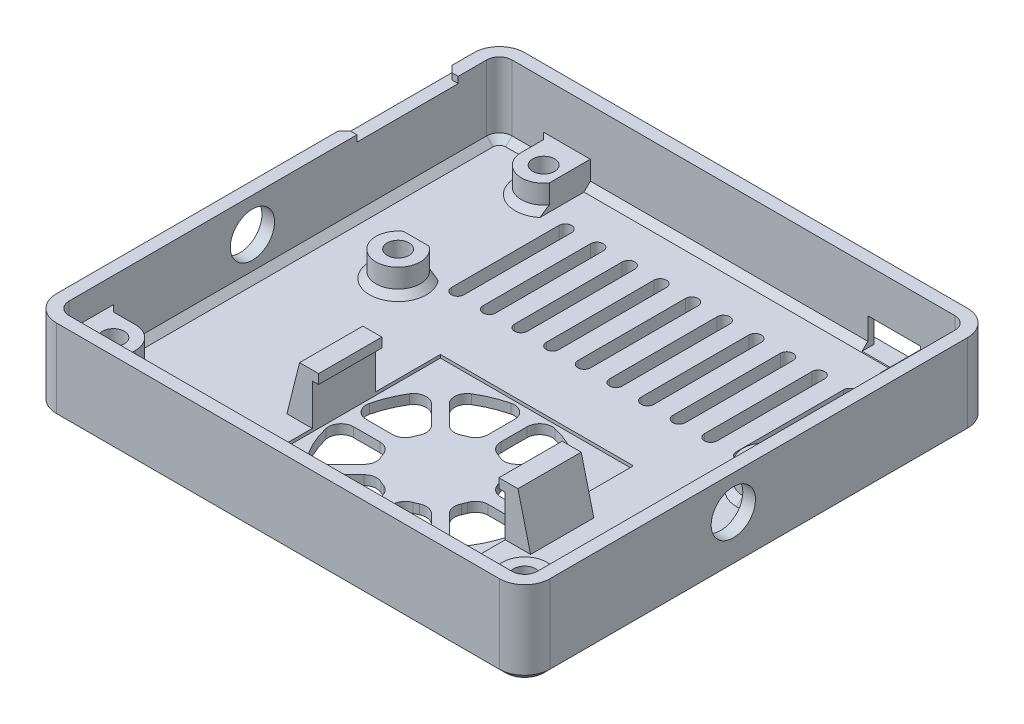
SolidWorks part; units mm, degrees
ref_plane "Front Plane" through (0, 0, 0) normal (0, 0, 1) x (1, 0, 0)
ref_plane "Top Plane" through (0, 0, 0) normal (0, 1, 0) x (1, 0, 0)
ref_plane "Right Plane" through (0, 0, 0) normal (1, 0, 0) x (0, 0, -1)
sketch "Sketch1" plane through (0, 0, 0) normal (0, 1, 0) x (1, 0, 0)
  line L0 (-65.617, -16.3721) -> (-0.617, -16.3721)
  line L1 (-62.117, 10.1279) -> (-4.117, 10.1279)
  line L2 (-62.117, 10.1279) -> (-62.117, -12.8721)
  line L3 (-65.617, 13.6279) -> (-0.617, 13.6279)
  line L4 (-65.617, 13.6279) -> (-65.617, -16.3721)
  line L5 (-62.117, -12.8721) -> (-4.117, -12.8721)
  line L6 (-0.617, 13.6279) -> (-0.617, -16.3721)
  line L7 (-4.117, 10.1279) -> (-4.117, -12.8721)
  line L8 (-24.217, 16.7282) -> (-24.217, 15.4455)
  line L9 (-11.617, 16.7282) -> (-11.617, 15.4455)
  dimension "D1" = 65
  dimension "D2" = 30
  dimension "D3" = 58
  dimension "D4" = 23
  dimension "D5" = 3.5
  dimension "D6" = 3.5
sketch "Sketch2" plane through (0, 0, 0) normal (0, 1, 0) x (1, 0, 0)
  line L6 (-73.617, 13.6279) -> (-73.617, -16.3721)
  line L7 (-73.617, 12.6279) -> (-73.617, -53.3721)
  line L10 (-71.617, -55.3721) -> (-1.617, -55.3721)
  line L11 (-75.617, 12.6279) -> (-75.617, -53.3721)
  line L12 (0.383, 14.6279) -> (0.383, -16.3721)
  line L13 (-65.617, 14.6279) -> (0.383, 14.6279)
  line L14 (0.383, 12.6279) -> (0.383, -53.3721)
  line L15 (-71.617, 14.6279) -> (-1.617, 14.6279)
  line L16 (-71.617, -57.3721) -> (-1.617, -57.3721)
  line L17 (2.383, 12.6279) -> (2.383, -53.3721)
  line L18 (-71.617, 16.6279) -> (-1.617, 16.6279)
  arc A0 (-71.617, -55.3721) -> (-73.617, -53.3721) centre (-71.617, -53.3721) cw
  arc A1 (-1.617, -55.3721) -> (0.383, -53.3721) centre (-1.617, -53.3721) ccw
  arc A2 (0.383, 12.6279) -> (-1.617, 14.6279) centre (-1.617, 12.6279) ccw
  arc A3 (-71.617, 14.6279) -> (-73.617, 12.6279) centre (-71.617, 12.6279) ccw
  arc A4 (-71.617, -57.3721) -> (-75.617, -53.3721) centre (-71.617, -53.3721) cw
  arc A5 (-1.617, -57.3721) -> (2.383, -53.3721) centre (-1.617, -53.3721) ccw
  arc A6 (2.383, 12.6279) -> (-1.617, 16.6279) centre (-1.617, 12.6279) ccw
  arc A7 (-71.617, 16.6279) -> (-75.617, 12.6279) centre (-71.617, 12.6279) ccw
  dimension "D4" = 2
  dimension "D3" = 70
  dimension "D1" = 8
  dimension "D2" = 1
  dimension "D5" = 2
extrude "Boss-Extrude1" add sketch "Sketch2" along normal blind 13.4
extrude "Boss-Extrude2" add sketch "Sketch2<3>" along normal blind 2 contours L15 A3 L7 A0 L10 A1 L14 A2 region at (-36.617, 0, 20.3721)
sketch "Sketch2<3>" plane through (0, 0, 0) normal (0, 1, 0) x (1, 0, 0) same geometry as "Sketch2"
sketch "Sketch4" plane through (0, 2, 0) normal (0, 1, 0) x (1, 0, 0)
  line L0 (-59.2343, 14.6279) -> (-59.2343, 8.1428)
  line L1 (-1.617, 14.6279) -> (-71.617, 14.6279) construction
  line L2 (-4.117, 6.6279) -> (0.383, 6.6279)
  line L3 (0.383, -53.3721) -> (0.383, 12.6279) construction
  line L4 (0.383, 6.6279) -> (0.383, 12.6279)
  line L5 (-7.0825, 14.6279) -> (-1.617, 14.6279)
  line L6 (-4.117, -9.3721) -> (0.383, -9.3721)
  line L7 (0.383, -9.3721) -> (0.383, -16.3721)
  line L8 (0.383, -16.3721) -> (-4.117, -16.3721)
  line L9 (-64.1397, -10.0158) -> (-60.0943, -10.0158)
  line L10 (-59.2343, 14.6279) -> (-65.617, 14.6279)
  line L11 (-65.617, 14.6279) -> (-65.617, 10.1279)
  line L12 (-7.0825, 14.6279) -> (-7.0825, 8.269)
  arc A0 (-7.0825, 8.269) -> (-4.117, 6.6279) centre (-4.117, 10.1279) ccw
  arc A1 (-4.117, -9.3721) -> (-4.117, -16.3721) centre (-4.117, -12.8721) ccw
  arc A2 (-64.1397, -10.0158) -> (-60.0943, -10.0158) centre (-62.117, -12.8721) ccw
  arc A3 (-65.617, 10.1279) -> (-59.2343, 8.1428) centre (-62.117, 10.1279) ccw
  arc A4 (0.383, 12.6279) -> (-1.617, 14.6279) centre (-1.617, 12.6279) ccw
  dimension "D1" = 2
extrude "Boss-Extrude3" add sketch "Sketch4" along normal offset from surface (4 mm away) 7.4 up to face at (-36.617, 13.4, 20.3721)
hole_wizard "CSK for #4 Flat Head Socket Cap Screw1" positions "Sketch6" profile "Sketch5" countersink size "#4" standard "ANSI Inch" end condition through all
sketch "Sketch6" plane through (0, 0, 0) normal (0, -1, 0) x (-1, 0, 0)
  point P0 (4.117, 10.1279)
  point P4 (62.117, 10.1279)
  point P8 (4.117, -12.8721)
  point P12 (62.117, -12.8721)
sketch "Sketch5" plane through (-4.117, 0, -10.1279) normal (1, 0, 0) x (0, 0, -1)
  line L0 (0, 0) -> (0, 13.4)
  line L1 (0, 13.4) -> (1.7272, 13.4)
  line L2 (1.7272, 13.4) -> (1.7272, 1.8805)
  line L3 (1.7272, 1.8805) -> (3.3619, 0)
  line L5 (3.3619, 0) -> (0, 0)
  line L6 (-1.7272, 1.8805) -> (-3.3619, 0) construction
  line L11 (0, -6.35) -> (0, 107.95) construction
  dimension "Thru Hole Dia." = 3.4544
  dimension "Thru Hole Depth" = 13.4
  dimension "Near C'Sink Dia." = 6.7237
  dimension "Near C'Sink Angle" = 82
sketch "Sketch7" plane through (0, 0, -16.6279) normal (0, 0, -1) x (-1, 0, 0)
  line L0 (11.2325, 6.5) -> (11.2325, 2.1) construction
  line L1 (7.0825, 6.5) -> (15.3825, 6.5)
  line L2 (7.0825, 6.5) -> (7.0825, 2.1)
  line L3 (7.0825, 2.1) -> (15.3825, 2.1)
  line L4 (15.3825, 6.5) -> (15.3825, 2.1)
  line L5 (1.617, 6) -> (7.0825, 6) construction
  line L7 (7.0825, 6) -> (7.0825, 2) construction
  dimension "D1" = 8.3
  dimension "D2" = 0.5
  dimension "D3" = 0
  dimension "D4" = 4.4
extrude "Cut-Extrude1" cut sketch "Sketch7" against normal up to next
sketch "Sketch9" plane through (0, 2, 0) normal (0, 1, 0) x (1, 0, 0)
  line L0 (0.383, -16.3721) -> (0.383, -53.3721) construction
  line L1 (-71.617, -55.3721) -> (-1.617, -55.3721) construction
  line L2 (-73.617, 12.6279) -> (-73.617, -53.3721) construction
  line L3 (-69.117, -47.3721) -> (-73.617, -47.3721)
  line L4 (-65.617, -50.8721) -> (-65.617, -55.3721)
  line L5 (-71.617, -55.3721) -> (-1.617, -55.3721) construction
  line L6 (-73.617, -47.3721) -> (-73.617, -53.3721)
  line L7 (-65.617, -55.3721) -> (-71.617, -55.3721)
  line L8 (-4.117, -47.3721) -> (0.383, -47.3721)
  line L9 (0.383, -47.3721) -> (0.383, -53.3721)
  line L10 (-7.617, -50.8721) -> (-7.617, -55.3721)
  line L11 (-7.617, -55.3721) -> (-1.617, -55.3721)
  arc A0 (-4.117, -47.3721) -> (-7.617, -50.8721) centre (-4.117, -50.8721) ccw
  arc A1 (-65.617, -50.8721) -> (-69.117, -47.3721) centre (-69.117, -50.8721) ccw
  arc A2 (-73.617, -53.3721) -> (-71.617, -55.3721) centre (-71.617, -53.3721) ccw
  arc A3 (-1.617, -55.3721) -> (0.383, -53.3721) centre (-1.617, -53.3721) ccw
  dimension "D1" = 4.5
  dimension "D2" = 4.5
  dimension "D3" = 4.5
  dimension "D4" = 4.5
  dimension "D5" = 2
  dimension "D6" = 2
extrude "Boss-Extrude4" add sketch "Sketch9" along normal offset from surface (7.4 mm away) 4 up to face at (-36.617, 13.4, 20.3721)
hole_wizard "CSK for #4 Flat Head Socket Cap Screw2" positions "Sketch11" profile "Sketch10" countersink size "#4" standard "ANSI Inch" end condition through all
sketch "Sketch11" plane through (0, 0, 0) normal (0, -1, 0) x (-1, 0, 0)
  point P0 (4.117, -50.8721)
  point P4 (69.117, -50.8721)
sketch "Sketch10" plane through (-4.117, 0, 50.8721) normal (1, 0, 0) x (0, 0, -1)
  line L0 (0, 0) -> (0, 13.4)
  line L1 (0, 13.4) -> (1.7272, 13.4)
  line L2 (1.7272, 13.4) -> (1.7272, 1.8805)
  line L3 (1.7272, 1.8805) -> (3.3619, 0)
  line L5 (3.3619, 0) -> (0, 0)
  line L6 (-1.7272, 1.8805) -> (-3.3619, 0) construction
  line L11 (0, -6.35) -> (0, 107.95) construction
  dimension "Thru Hole Dia." = 3.4544
  dimension "Thru Hole Depth" = 13.4
  dimension "Near C'Sink Dia." = 6.7237
  dimension "Near C'Sink Angle" = 82
chamfer "Chamfer1" distance 1 angle 45 8 edges at (-65.617, 4, -14.6279) (-65.617, 5.7, 55.3721) (-73.617, 5.7, 47.3721) (0.383, 4, 9.3721) (0.383, 4, -6.6279) (0.383, 4, 16.3721) (0.383, 5.7, 47.3721) (-7.617, 5.7, 55.3721)
chamfer "Chamfer2" distance 1 angle 45 21 edges at (-62.117, 2, 16.3721) (-65.617, 2, -11.8779) (-63.1564, 2, -6.7858) (-2.367, 2, -6.6279) (-5.8117, 2, -7.0655) (0.383, 2, 1.3721) (-2.367, 2, 9.3721) (-2.367, 2, 16.3721) (0.383, 2, 31.8721) (-2.367, 2, 47.3721) (-7.617, 2, 52.6221) (-6.5919, 2, 48.3973) (-36.617, 2, 55.3721) (-65.617, 2, 52.6221) (-70.867, 2, 47.3721) (-66.6421, 2, 48.3973) (-69.117, 2, -14.6279) (-73.0312, 2, -14.0421) (-73.617, 2, 16.8721) (-7.617, 2, 12.8721) (-33.1584, 2, -14.6279)
chamfer "Chamfer3" distance 1 angle 45 8 edges at (2.383, 0, 20.3721) (1.2114, 0, -15.4563) (1.2114, 0, 56.2006) (-36.617, 0, -16.6279) (-36.617, 0, 57.3721) (-74.4454, 0, -15.4563) (-74.4454, 0, 56.2006) (-75.617, 0, 20.3721)
chamfer "Chamfer4" distance 1 angle 45 2 edges at (-15.3825, 4.3, -16.6279) (-7.0825, 4.3, -16.6279)
sketch "Sketch12" plane through (0, 0, 0) normal (0, -1, 0) x (1, 0, 0)
  line L0 (-55.6605, 9.9113) -> (-55.6605, -7.0887) construction
  line L1 (-54.6605, 9.9113) -> (-54.6605, -7.0887)
  line L2 (-56.6605, 9.9113) -> (-56.6605, -7.0887)
  line L3 (-50.6605, 9.9113) -> (-50.6605, -7.0887) construction
  line L4 (-49.6605, 9.9113) -> (-49.6605, -7.0887)
  line L5 (-51.6605, 9.9113) -> (-51.6605, -7.0887)
  line L6 (-45.6605, 9.9113) -> (-45.6605, -7.0887) construction
  line L7 (-44.6605, 9.9113) -> (-44.6605, -7.0887)
  line L8 (-46.6605, 9.9113) -> (-46.6605, -7.0887)
  line L9 (-40.6605, 9.9113) -> (-40.6605, -7.0887) construction
  line L10 (-39.6605, 9.9113) -> (-39.6605, -7.0887)
  line L11 (-41.6605, 9.9113) -> (-41.6605, -7.0887)
  line L12 (-35.6605, 9.9113) -> (-35.6605, -7.0887) construction
  line L13 (-34.6605, 9.9113) -> (-34.6605, -7.0887)
  line L14 (-36.6605, 9.9113) -> (-36.6605, -7.0887)
  line L15 (-30.6605, 9.9113) -> (-30.6605, -7.0887) construction
  line L16 (-29.6605, 9.9113) -> (-29.6605, -7.0887)
  line L17 (-31.6605, 9.9113) -> (-31.6605, -7.0887)
  line L18 (-25.6605, 9.9113) -> (-25.6605, -7.0887) construction
  line L19 (-24.6605, 9.9113) -> (-24.6605, -7.0887)
  line L20 (-26.6605, 9.9113) -> (-26.6605, -7.0887)
  line L21 (-20.6605, 9.9113) -> (-20.6605, -7.0887) construction
  line L22 (-19.6605, 9.9113) -> (-19.6605, -7.0887)
  line L23 (-21.6605, 9.9113) -> (-21.6605, -7.0887)
  line L24 (-15.6605, 9.9113) -> (-15.6605, -7.0887) construction
  line L25 (-14.6605, 9.9113) -> (-14.6605, -7.0887)
  line L26 (-16.6605, 9.9113) -> (-16.6605, -7.0887)
  line L27 (-10.6605, 9.9113) -> (-10.6605, -7.0887) construction
  line L28 (-9.6605, 9.9113) -> (-9.6605, -7.0887)
  line L29 (-11.6605, 9.9113) -> (-11.6605, -7.0887)
  arc A0 (-54.6605, 9.9113) -> (-56.6605, 9.9113) centre (-55.6605, 9.9113) ccw
  arc A1 (-56.6605, -7.0887) -> (-54.6605, -7.0887) centre (-55.6605, -7.0887) ccw
  arc A2 (-49.6605, 9.9113) -> (-51.6605, 9.9113) centre (-50.6605, 9.9113) ccw
  arc A3 (-51.6605, -7.0887) -> (-49.6605, -7.0887) centre (-50.6605, -7.0887) ccw
  arc A4 (-44.6605, 9.9113) -> (-46.6605, 9.9113) centre (-45.6605, 9.9113) ccw
  arc A5 (-46.6605, -7.0887) -> (-44.6605, -7.0887) centre (-45.6605, -7.0887) ccw
  arc A6 (-39.6605, 9.9113) -> (-41.6605, 9.9113) centre (-40.6605, 9.9113) ccw
  arc A7 (-41.6605, -7.0887) -> (-39.6605, -7.0887) centre (-40.6605, -7.0887) ccw
  arc A8 (-34.6605, 9.9113) -> (-36.6605, 9.9113) centre (-35.6605, 9.9113) ccw
  arc A9 (-36.6605, -7.0887) -> (-34.6605, -7.0887) centre (-35.6605, -7.0887) ccw
  arc A10 (-29.6605, 9.9113) -> (-31.6605, 9.9113) centre (-30.6605, 9.9113) ccw
  arc A11 (-31.6605, -7.0887) -> (-29.6605, -7.0887) centre (-30.6605, -7.0887) ccw
  arc A12 (-24.6605, 9.9113) -> (-26.6605, 9.9113) centre (-25.6605, 9.9113) ccw
  arc A13 (-26.6605, -7.0887) -> (-24.6605, -7.0887) centre (-25.6605, -7.0887) ccw
  arc A14 (-19.6605, 9.9113) -> (-21.6605, 9.9113) centre (-20.6605, 9.9113) ccw
  arc A15 (-21.6605, -7.0887) -> (-19.6605, -7.0887) centre (-20.6605, -7.0887) ccw
  arc A16 (-14.6605, 9.9113) -> (-16.6605, 9.9113) centre (-15.6605, 9.9113) ccw
  arc A17 (-16.6605, -7.0887) -> (-14.6605, -7.0887) centre (-15.6605, -7.0887) ccw
  arc A18 (-9.6605, 9.9113) -> (-11.6605, 9.9113) centre (-10.6605, 9.9113) ccw
  arc A19 (-11.6605, -7.0887) -> (-9.6605, -7.0887) centre (-10.6605, -7.0887) ccw
  point P2 (-55.6605, 1.4113)
  point P10 (-50.6605, 1.4113)
  point P17 (-45.6605, 1.4113)
  point P24 (-40.6605, 1.4113)
  point P31 (-35.6605, 1.4113)
  point P38 (-30.6605, 1.4113)
  point P45 (-25.6605, 1.4113)
  point P52 (-20.6605, 1.4113)
  point P59 (-15.6605, 1.4113)
  point P66 (-10.6605, 1.4113)
  dimension "D1" = 2
  dimension "D2" = 17
  dimension "D3" = 10
extrude "Cut-Extrude2" cut sketch "Sketch12" against normal up to next
sketch "Sketch13" plane through (0, 2, 0) normal (0, 1, 0) x (1, 0, 0)
  line L1 (-17.867, -50.4402) -> (-48.367, -50.4402)
  line L2 (-17.867, -50.4402) -> (-17.867, -19.9402)
  line L3 (-17.867, -19.9402) -> (-48.367, -19.9402)
  line L4 (-48.367, -50.4402) -> (-48.367, -19.9402)
  dimension "D1" = 30.5
  dimension "D2" = 30.5
extrude "Cut-Extrude3" cut sketch "Sketch13" against normal blind 0.5
sketch "Sketch14" plane through (0, 2, 0) normal (0, 1, 0) x (1, 0, 0)
  line L0 (-48.367, -40.1902) -> (-50.367, -40.1902)
  line L1 (-15.867, -40.1902) -> (-17.867, -40.1902)
  line L2 (-15.867, -40.1902) -> (-15.867, -30.1902)
  line L3 (-15.867, -30.1902) -> (-17.867, -30.1902)
  line L4 (-17.867, -40.1902) -> (-17.867, -30.1902)
  line L5 (-48.367, -30.1902) -> (-50.367, -30.1902)
  line L6 (-50.367, -40.1902) -> (-50.367, -30.1902)
  line L7 (-48.367, -40.1902) -> (-48.367, -30.1902)
  dimension "D1" = 10
  dimension "D2" = 2
  dimension "D3" = 10
extrude "Boss-Extrude5" add sketch "Sketch14" along normal blind 8
sketch "Sketch15" plane through (-17.867, 0, 0) normal (-1, 0, 0) x (0, 0, 1)
  line L0 (30.1902, 10) -> (30.1902, 2) construction
  line L1 (40.1902, 10) -> (30.1902, 10)
  line L2 (40.1902, 10) -> (40.1902, 8.5)
  line L3 (40.1902, 8.5) -> (30.1902, 8.5)
  line L4 (30.1902, 10) -> (30.1902, 8.5)
  line L5 (30.1902, 10) -> (40.1902, 10) construction
  dimension "D1" = 1.5
extrude "Boss-Extrude6" add sketch "Sketch15" along normal blind 1
sketch "Sketch16" plane through (-48.367, 0, 0) normal (1, 0, 0) x (0, 0, -1)
  line L0 (-30.1902, 10) -> (-30.1902, 2) construction
  line L1 (-40.1902, 10) -> (-30.1902, 10)
  line L2 (-40.1902, 10) -> (-40.1902, 8.5)
  line L3 (-40.1902, 8.5) -> (-30.1902, 8.5)
  line L4 (-30.1902, 10) -> (-30.1902, 8.5)
  dimension "D1" = 1.5
extrude "Boss-Extrude7" add sketch "Sketch16" along normal blind 1
chamfer "Chamfer5" distance 2 angle 76 2 edges at (-50.367, 2, 35.1902) (-15.867, 2, 35.1902) first distance on face at (-10.6605, 2, 1.4113)
sketch "Sketch17" plane through (0, 1.5, 0) normal (0, 1, 0) x (1, 0, 0)
  line L0 (-41.3961, -25.4969) -> (-38.4532, -28.4398)
  line L1 (-34.117, -22.4818) -> (-34.117, -26.6437)
  line L2 (-32.117, -22.4818) -> (-32.117, -26.6437)
  line L3 (-24.8379, -25.4969) -> (-27.7808, -28.4398)
  line L4 (-23.4236, -26.9111) -> (-26.3666, -29.854)
  line L5 (-20.4085, -34.1902) -> (-24.5705, -34.1902)
  line L6 (-20.4085, -36.1902) -> (-24.5705, -36.1902)
  line L7 (-23.4236, -43.4693) -> (-26.3666, -40.5264)
  line L8 (-24.8379, -44.8835) -> (-27.7808, -41.9406)
  line L9 (-32.117, -47.8987) -> (-32.117, -43.7367)
  line L10 (-34.117, -47.8987) -> (-34.117, -43.7367)
  line L11 (-41.3961, -44.8835) -> (-38.4532, -41.9406)
  line L12 (-42.8103, -43.4693) -> (-39.8674, -40.5264)
  line L13 (-45.8254, -36.1902) -> (-41.6635, -36.1902)
  line L14 (-45.8254, -34.1902) -> (-41.6635, -34.1902)
  line L15 (-42.8103, -26.9111) -> (-39.8674, -29.854)
  arc A0 (-45.9258, -27.2738) -> (-47.7719, -31.7307) centre (-33.117, -35.1902) ccw
  arc A1 (-39.4788, -32.1342) -> (-39.7764, -32.8526) centre (-33.117, -35.1902) ccw
  arc A2 (-39.4788, -32.1342) -> (-39.8674, -29.854) centre (-41.2816, -31.2682) ccw
  arc A3 (-41.6635, -34.1902) -> (-39.7764, -32.8526) centre (-41.6635, -32.1902) ccw
  arc A4 (-45.8254, -34.1902) -> (-47.7719, -31.7307) centre (-45.8254, -32.1902) cw
  arc A5 (-42.8103, -26.9111) -> (-45.9258, -27.2738) centre (-44.2245, -28.3253) ccw
  arc A6 (-36.5765, -20.5353) -> (-41.0334, -22.3814) centre (-33.117, -35.1902) ccw
  arc A7 (-35.4546, -28.5308) -> (-36.173, -28.8284) centre (-33.117, -35.1902) ccw
  arc A8 (-35.4546, -28.5308) -> (-34.117, -26.6437) centre (-36.117, -26.6437) ccw
  arc A9 (-38.4532, -28.4398) -> (-36.173, -28.8284) centre (-37.039, -27.0256) ccw
  arc A10 (-41.3961, -25.4969) -> (-41.0334, -22.3814) centre (-39.9819, -24.0827) cw
  arc A11 (-34.117, -22.4818) -> (-36.5765, -20.5353) centre (-36.117, -22.4818) ccw
  arc A12 (-25.2006, -22.3814) -> (-29.6575, -20.5353) centre (-33.117, -35.1902) ccw
  arc A13 (-30.061, -28.8284) -> (-30.7794, -28.5308) centre (-33.117, -35.1902) ccw
  arc A14 (-30.061, -28.8284) -> (-27.7808, -28.4398) centre (-29.195, -27.0256) ccw
  arc A15 (-32.117, -26.6437) -> (-30.7794, -28.5308) centre (-30.117, -26.6437) ccw
  arc A16 (-32.117, -22.4818) -> (-29.6575, -20.5353) centre (-30.117, -22.4818) cw
  arc A17 (-24.8379, -25.4969) -> (-25.2006, -22.3814) centre (-26.2521, -24.0827) ccw
  arc A18 (-18.462, -31.7307) -> (-20.3081, -27.2738) centre (-33.117, -35.1902) ccw
  arc A19 (-26.4576, -32.8526) -> (-26.7552, -32.1342) centre (-33.117, -35.1902) ccw
  arc A20 (-26.4576, -32.8526) -> (-24.5705, -34.1902) centre (-24.5705, -32.1902) ccw
  arc A21 (-26.3666, -29.854) -> (-26.7552, -32.1342) centre (-24.9524, -31.2682) ccw
  arc A22 (-23.4236, -26.9111) -> (-20.3081, -27.2738) centre (-22.0094, -28.3253) cw
  arc A23 (-20.4085, -34.1902) -> (-18.462, -31.7307) centre (-20.4085, -32.1902) ccw
  arc A24 (-20.3081, -43.1066) -> (-18.462, -38.6497) centre (-33.117, -35.1902) ccw
  arc A25 (-26.7552, -38.2462) -> (-26.4576, -37.5278) centre (-33.117, -35.1902) ccw
  arc A26 (-26.7552, -38.2462) -> (-26.3666, -40.5264) centre (-24.9524, -39.1122) ccw
  arc A27 (-24.5705, -36.1902) -> (-26.4576, -37.5278) centre (-24.5705, -38.1902) ccw
  arc A28 (-20.4085, -36.1902) -> (-18.462, -38.6497) centre (-20.4085, -38.1902) cw
  arc A29 (-23.4236, -43.4693) -> (-20.3081, -43.1066) centre (-22.0094, -42.0551) ccw
  arc A30 (-29.6575, -49.8452) -> (-25.2006, -47.9991) centre (-33.117, -35.1902) ccw
  arc A31 (-30.7794, -41.8496) -> (-30.061, -41.552) centre (-33.117, -35.1902) ccw
  arc A32 (-30.7794, -41.8496) -> (-32.117, -43.7367) centre (-30.117, -43.7367) ccw
  arc A33 (-27.7808, -41.9406) -> (-30.061, -41.552) centre (-29.195, -43.3548) ccw
  arc A34 (-24.8379, -44.8835) -> (-25.2006, -47.9991) centre (-26.2521, -46.2978) cw
  arc A35 (-32.117, -47.8987) -> (-29.6575, -49.8452) centre (-30.117, -47.8987) ccw
  arc A36 (-41.0334, -47.9991) -> (-36.5765, -49.8452) centre (-33.117, -35.1902) ccw
  arc A37 (-36.173, -41.552) -> (-35.4546, -41.8496) centre (-33.117, -35.1902) ccw
  arc A38 (-36.173, -41.552) -> (-38.4532, -41.9406) centre (-37.039, -43.3548) ccw
  arc A39 (-34.117, -43.7367) -> (-35.4546, -41.8496) centre (-36.117, -43.7367) ccw
  arc A40 (-34.117, -47.8987) -> (-36.5765, -49.8452) centre (-36.117, -47.8987) cw
  arc A41 (-41.3961, -44.8835) -> (-41.0334, -47.9991) centre (-39.9819, -46.2978) ccw
  arc A42 (-47.7719, -38.6497) -> (-45.9258, -43.1066) centre (-33.117, -35.1902) ccw
  arc A43 (-39.7764, -37.5278) -> (-39.4788, -38.2462) centre (-33.117, -35.1902) ccw
  arc A44 (-39.7764, -37.5278) -> (-41.6635, -36.1902) centre (-41.6635, -38.1902) ccw
  arc A45 (-39.8674, -40.5264) -> (-39.4788, -38.2462) centre (-41.2816, -39.1122) ccw
  arc A46 (-42.8103, -43.4693) -> (-45.9258, -43.1066) centre (-44.2245, -42.0551) cw
  arc A47 (-45.8254, -36.1902) -> (-47.7719, -38.6497) centre (-45.8254, -38.1902) ccw
  point P41 (-33.117, -35.1902)
  point P98 (-33.117, -35.1902)
  dimension "D1" = 2
extrude "Cut-Extrude4" cut sketch "Sketch17" against normal through all
sketch "Sketch18" plane through (-73.617, 0, 0) normal (1, 0, 0) x (0, 0, -1)
  circle A0 centre (-24.3941, 7.9996) radius 3.5
  dimension "D1" = 7
extrude "Cut-Extrude5" cut sketch "Sketch18" against normal through all both and the other way through all
sketch "Sketch19" plane through (-75.617, 0, 0) normal (-1, 0, 0) x (0, 0, 1)
  line L0 (-12.6279, 13.4) -> (53.3721, 13.4) construction
  line L1 (-8.1279, 13.4) -> (7.8721, 13.4)
  line L2 (-8.1279, 13.4) -> (-8.1279, 12.4)
  line L3 (-8.1279, 12.4) -> (7.8721, 12.4)
  line L4 (7.8721, 13.4) -> (7.8721, 12.4)
  line L5 (-12.6279, 13.4) -> (-12.6279, 1) construction
  point P6 (-8.1279, 12.9)
  dimension "D1" = 16
  dimension "D2" = 4.5
  dimension "D3" = 1
extrude "Cut-Extrude6" cut sketch "Sketch19" against normal up to next
chamfer "Chamfer6" distance 1 angle 45 2 edges at (-75.617, 12.9, 7.8721) (-75.617, 12.9, -8.1279)
